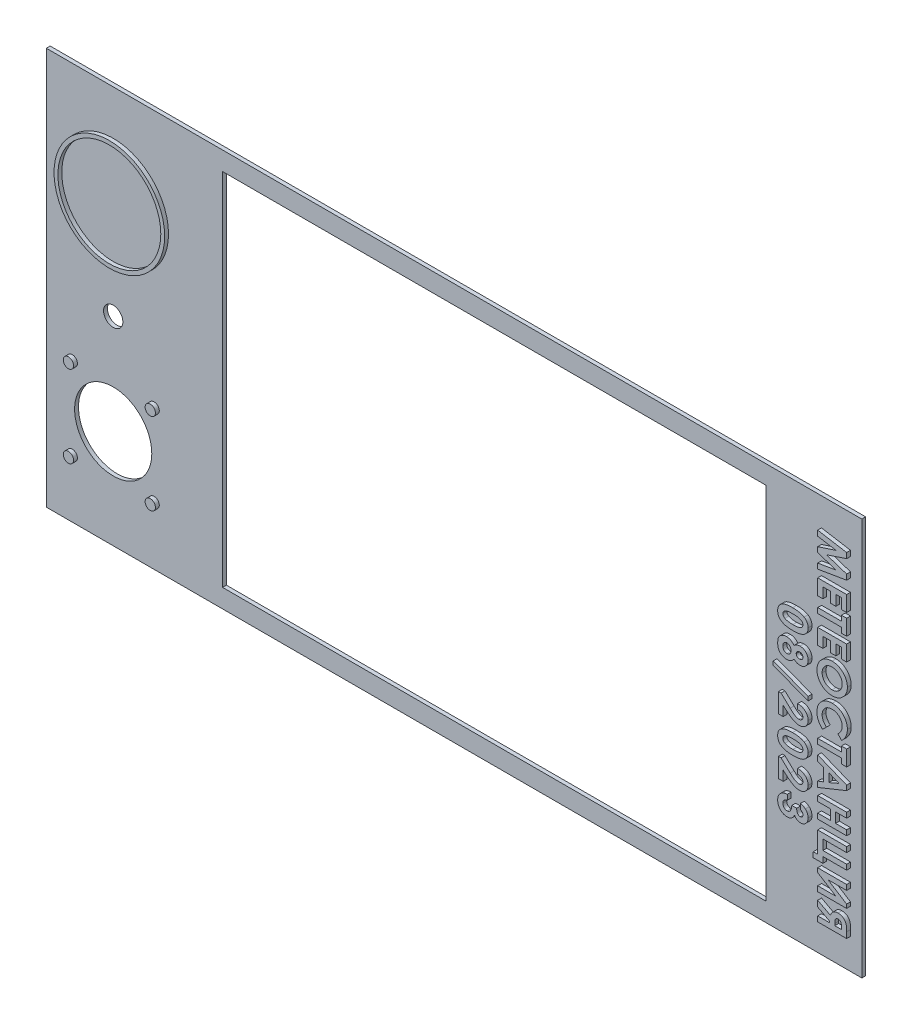
SolidWorks part; units mm, degrees
ref_plane "Спереди" through (0, 0, 0) normal (0, 0, 1) x (1, 0, 0)
ref_plane "Сверху" through (0, 0, 0) normal (0, 1, 0) x (1, 0, 0)
ref_plane "Справа" through (0, 0, 0) normal (1, 0, 0) x (0, 0, -1)
sketch "Эскиз1" plane through (0, 0, 0) normal (0, 0, 1) x (1, 0, 0)
  line L1 (-35.4452, 29.8258) -> (96.5548, 29.8258)
  line L2 (-35.4452, 29.8258) -> (-35.4452, -37.1742)
  line L3 (-35.4452, -37.1742) -> (96.5548, -37.1742)
  line L4 (96.5548, 29.8258) -> (96.5548, -37.1742)
  dimension "D1" = 67
  dimension "D2" = 132
extrude "Бобышка-Вытянуть1" add sketch "Эскиз1" against normal blind 10
shell "Оболочка1" thickness 2 removed face at (30.5548, -3.6742, -10) removed face at (30.5548, -3.6742, 0)
sketch "Эскиз3" plane through (0, 0, -10) normal (0, 0, -1) x (-1, 0, 0)
  line L1 (-96.5548, 29.8258) -> (35.4452, 29.8258)
  line L2 (-96.5548, 29.8258) -> (-96.5548, -37.1742)
  line L3 (-96.5548, -37.1742) -> (35.4452, -37.1742)
  line L4 (35.4452, 29.8258) -> (35.4452, -37.1742)
  line L5 (34.6452, -36.3742) -> (-95.7548, -36.3742)
  line L6 (34.6452, -36.3742) -> (34.6452, 29.0258)
  line L7 (34.6452, 29.0258) -> (-95.7548, 29.0258)
  line L8 (-95.7548, -36.3742) -> (-95.7548, 29.0258)
  dimension "D1" = 0.8
  dimension "D2" = 0.8
  dimension "D3" = 0.8
  dimension "D4" = 0.8
extrude "Бобышка-Вытянуть2" add sketch "Эскиз3" along normal blind 2
sketch "Эскиз4" plane through (0, 0, 0) normal (0, 0, 1) x (1, 0, 0)
  line L1 (-35.4452, 29.8258) -> (96.5548, 29.8258)
  line L2 (-35.4452, 29.8258) -> (-35.4452, -37.1742)
  line L3 (-35.4452, -37.1742) -> (96.5548, -37.1742)
  line L4 (96.5548, 29.8258) -> (96.5548, -37.1742)
extrude "Бобышка-Вытянуть3" add sketch "Эскиз4" against normal blind 2
sketch "Эскиз5" plane through (0, 0, -2) normal (0, 0, -1) x (-1, 0, 0)
  line L0 (33.4452, 27.8258) -> (-94.5548, 27.8258) construction
  line L1 (-85.5548, 24.8258) -> (-0.5548, 24.8258)
  line L2 (-85.5548, 24.8258) -> (-85.5548, -32.1742)
  line L3 (-85.5548, -32.1742) -> (-0.5548, -32.1742)
  line L4 (-0.5548, 24.8258) -> (-0.5548, -32.1742)
  line L5 (-94.5548, -35.1742) -> (33.4452, -35.1742) construction
  line L6 (-94.5548, 27.8258) -> (-94.5548, -35.1742) construction
  dimension "D1" = 3
  dimension "D2" = 3
  dimension "D3" = 9
  dimension "D4" = 85
  dimension "D5" = 57
extrude "Вырез-Вытянуть2" cut sketch "Эскиз5" against normal blind 2
sketch "Эскиз6" plane through (0, 0, -2) normal (0, 0, -1) x (-1, 0, 0)
  circle A0 centre (21.9452, -3.6742) radius 3.5
  dimension "D1" = 7
extrude "Вырез-Вытянуть3" cut sketch "Эскиз6" against normal blind 2
sketch "Эскиз7" plane through (0, 0, 0) normal (0, 0, 1) x (1, 0, 0)
  line L5 (-32.9452, 27.3258) -> (94.0548, 27.3258)
  line L6 (-32.9452, 27.3258) -> (-32.9452, -34.6742)
  line L7 (-32.9452, -34.6742) -> (94.0548, -34.6742)
  line L8 (94.0548, 27.3258) -> (94.0548, -34.6742)
extrude "Вырез-Вытянуть4" cut sketch "Эскиз7" against normal blind 0.8
sketch "Эскиз8" plane through (95.7548, 0, 0) normal (-1, 0, 0) x (0, 0, 1)
  line L1 (-11.2, 23.4258) -> (-12, 23.4258)
  line L2 (-11.2, 23.4258) -> (-11.2, 5.6258)
  line L3 (-11.2, 5.6258) -> (-12, 5.6258)
  line L4 (-12, 23.4258) -> (-12, 5.6258)
  line L5 (-11.2, -12.9742) -> (-12, -12.9742)
  line L6 (-11.2, -12.9742) -> (-11.2, -30.7742)
  line L7 (-11.2, -30.7742) -> (-12, -30.7742)
  line L8 (-12, -12.9742) -> (-12, -30.7742)
  dimension "D1" = 17.8
  dimension "D2" = 17.8
extrude "Бобышка-Вытянуть4" add sketch "Эскиз8" along normal blind 1.2
sketch "Эскиз9" plane through (0, 0, -12) normal (0, 0, -1) x (-1, 0, 0)
  line L1 (-94.5548, 27.8258) -> (33.4452, 27.8258)
  line L2 (-94.5548, 27.8258) -> (-94.5548, -35.1742)
  line L3 (-94.5548, -35.1742) -> (33.4452, -35.1742)
  line L4 (33.4452, 27.8258) -> (33.4452, -35.1742)
  line L5 (34.6452, -36.3742) -> (-95.7548, -36.3742)
  line L6 (34.6452, -36.3742) -> (34.6452, 29.0258)
  line L7 (34.6452, 29.0258) -> (-95.7548, 29.0258)
  line L8 (-95.7548, -36.3742) -> (-95.7548, 29.0258)
extrude "Бобышка-Вытянуть5" add sketch "Эскиз9" against normal blind 2
sketch "Эскиз10" plane through (0, 0, -12) normal (0, 0, -1) x (-1, 0, 0)
  line L0 (33.4452, 27.8258) -> (-94.5548, 27.8258) construction
  line L1 (-96.5548, 29.8258) -> (35.4452, 29.8258)
  line L2 (-96.5548, 29.8258) -> (-96.5548, -37.1742)
  line L3 (-96.5548, -37.1742) -> (35.4452, -37.1742)
  line L4 (35.4452, 29.8258) -> (35.4452, -37.1742)
  line L5 (34.2452, -35.9742) -> (-95.3548, -35.9742)
  line L6 (34.2452, -35.9742) -> (34.2452, 28.6258)
  line L7 (34.2452, 28.6258) -> (-95.3548, 28.6258)
  line L8 (-95.3548, -35.9742) -> (-95.3548, 28.6258)
  line L9 (-94.5548, 27.8258) -> (-94.5548, -35.1742) construction
  line L10 (-94.5548, -35.1742) -> (33.4452, -35.1742) construction
  line L11 (33.4452, -35.1742) -> (33.4452, 27.8258) construction
  dimension "D1" = 0.8
  dimension "D2" = 0.8
  dimension "D3" = 0.8
  dimension "D4" = 0.8
extrude "Вырез-Вытянуть5" cut sketch "Эскиз10" against normal blind 2
sketch "Эскиз11" plane through (0, 0, -2) normal (0, 0, -1) x (-1, 0, 0)
  line L0 (-94.5548, 27.8258) -> (-94.5548, -35.1742) construction
  line L1 (-87.0548, 27.0758) -> (7.9452, 27.0758)
  line L2 (-87.0548, 27.0758) -> (-87.0548, -34.4242)
  line L3 (-87.0548, -34.4242) -> (7.9452, -34.4242)
  line L4 (7.9452, 27.0758) -> (7.9452, -34.4242)
  line L5 (33.4452, 27.8258) -> (-94.5548, 27.8258) construction
  line L6 (-94.5548, -35.1742) -> (33.4452, -35.1742) construction
  dimension "D1" = 7.5
  dimension "D2" = 95
  dimension "D3" = 0.75
  dimension "D4" = 0.75
  dimension "D5" = 61.5
extrude "Вырез-Вытянуть6" cut sketch "Эскиз11" against normal blind 2
sketch "Эскиз12" plane through (0, 0, 0) normal (0, 0, 1) x (1, 0, 0)
  line L0 (96.5548, -37.1742) -> (96.5548, 29.8258) construction
  line L1 (-33.4452, 27.8258) -> (94.5548, 27.8258)
  line L2 (-33.4452, 27.8258) -> (-33.4452, -35.1742)
  line L3 (-33.4452, -35.1742) -> (94.5548, -35.1742)
  line L4 (94.5548, 27.8258) -> (94.5548, -35.1742)
  line L5 (-35.4452, -37.1742) -> (96.5548, -37.1742) construction
  line L6 (-35.4452, 29.8258) -> (-35.4452, -37.1742) construction
  line L7 (96.5548, 29.8258) -> (-35.4452, 29.8258) construction
  dimension "D1" = 2
  dimension "D2" = 2
  dimension "D3" = 2
  dimension "D4" = 2
extrude "Вырез-Вытянуть7" cut sketch "Эскиз12" against normal blind 0.8
sketch "Эскиз14" plane through (0, 0, -2) normal (0, 0, -1) x (-1, 0, 0)
  line L0 (33.4452, 27.8258) -> (-94.5548, 27.8258) construction
  line L1 (-94.5548, -35.1742) -> (33.4452, -35.1742) construction
  line L2 (-94.5548, -28.0242) -> (-94.5548, -35.1742)
  line L3 (-94.5548, 27.8258) -> (-94.5548, -35.1742) construction
  line L4 (7.9452, -34.4242) -> (7.9452, 27.0758) construction
  line L5 (-87.0548, 27.0758) -> (-87.0548, -34.4242) construction
  line L6 (-94.5548, -35.1742) -> (-87.5548, -35.1742)
  line L7 (-87.5548, -35.1742) -> (-87.5548, -31.5242)
  line L9 (-91.0548, -28.0242) -> (-94.5548, -28.0242)
  line L11 (-87.5548, 24.1758) -> (-87.5548, 27.8258)
  line L12 (-87.5548, 27.8258) -> (-94.5548, 27.8258)
  line L13 (-94.5548, 27.8258) -> (-94.5548, 20.6758)
  line L14 (-94.5548, 20.6758) -> (-91.0548, 20.6758)
  line L15 (7.4452, 24.1758) -> (7.4452, 27.8258)
  line L16 (7.4452, 27.8258) -> (14.4452, 27.8258)
  line L17 (33.4452, 27.8258) -> (-94.5548, 27.8258) construction
  line L18 (14.4452, 27.8258) -> (14.4452, 24.1758)
  line L19 (7.4452, -31.5242) -> (7.4452, -35.1742)
  line L20 (7.4452, -35.1742) -> (14.4452, -35.1742)
  line L21 (-94.5548, -35.1742) -> (33.4452, -35.1742) construction
  line L22 (14.4452, -35.1742) -> (14.4452, -31.5242)
  circle A0 centre (-91.0548, 24.1758) radius 1.2
  circle A1 centre (-91.0548, -31.5242) radius 1.2
  circle A2 centre (10.9452, 24.1758) radius 1.2
  circle A3 centre (10.9452, -31.5242) radius 1.2
  arc A4 (-91.0548, -28.0242) -> (-87.5548, -31.5242) centre (-91.0548, -31.5242) cw
  arc A5 (-87.5548, 24.1758) -> (-91.0548, 20.6758) centre (-91.0548, 24.1758) cw
  arc A6 (7.4452, 24.1758) -> (14.4452, 24.1758) centre (10.9452, 24.1758) ccw
  arc A7 (14.4452, -31.5242) -> (7.4452, -31.5242) centre (10.9452, -31.5242) ccw
  dimension "D1" = 3.65
  dimension "D2" = 3.65
  dimension "D5" = 3.5
  dimension "D6" = 3.5
  dimension "D7" = 102
  dimension "D8" = 102
  dimension "D9" = 55.7
  dimension "D10" = 3
  dimension "D11" = 4
extrude "Бобышка-Вытянуть6" add sketch "Эскиз14" along normal blind 1.8
sketch "Эскиз15" plane through (0, 0, -0.8) normal (0, 0, 1) x (1, 0, 0)
  line L1 (-7.9452, 27.0758) -> (-7.4452, 27.0758)
  line L2 (-7.9452, 27.0758) -> (-7.9452, -34.4242)
  line L3 (-7.9452, -34.4242) -> (-7.4452, -34.4242)
  line L4 (-7.4452, 27.0758) -> (-7.4452, -34.4242)
extrude "Бобышка-Вытянуть7" add sketch "Эскиз15" against normal up to surface (1.2 mm away) up to face at (-7.6645, -32.515, -2)
sketch "Эскиз16" plane through (0, 0, -2) normal (0, 0, -1) x (-1, 0, 0)
  line L0 (-87.5548, -35.1742) -> (-87.5548, -31.5242) construction
  line L1 (-87.0548, 27.0758) -> (-87.5548, 27.0758)
  line L2 (-87.0548, 27.0758) -> (-87.0548, -34.4242)
  line L3 (-87.0548, -34.4242) -> (-87.5548, -34.4242)
  line L4 (-87.5548, 27.0758) -> (-87.5548, -34.4242)
extrude "Вырез-Вытянуть8" cut sketch "Эскиз16" against normal blind 1.8
sketch "Эскиз17" plane through (0, 0, -2) normal (0, 0, -1) x (-1, 0, 0)
  circle A0 centre (-91.0548, 24.1758) radius 1.2
  circle A1 centre (-91.0548, -31.5242) radius 1.2
  circle A2 centre (10.9452, -31.5242) radius 1.2
  circle A5 centre (10.9452, 24.1758) radius 1.2
extrude "Вырез-Вытянуть9" cut sketch "Эскиз17" against normal blind 1.8
sketch "Эскиз19" plane through (0, 0, -2) normal (0, 0, -1) x (-1, 0, 0)
  line L0 (33.4452, -35.1742) -> (33.4452, 27.8258) construction
  line L1 (14.4452, -35.1742) -> (33.4452, -35.1742) construction
  line L2 (14.4452, -35.1742) -> (14.4452, -31.5242) construction
  circle A0 centre (22.4452, -19.1742) radius 3.5
  point P8 (14.4452, -33.3492)
  dimension "D1" = 11
  dimension "D2" = 16
  dimension "D3" = 8
extrude "Вырез-Вытянуть11" cut sketch "Эскиз19" against normal blind 1.8
sketch "Эскиз22" plane through (0, 0, -2) normal (0, 0, -1) x (-1, 0, 0)
  circle A0 centre (21.9452, -3.6742) radius 3.5
extrude "Бобышка-Вытянуть9" add sketch "Эскиз22" against normal up to surface (1.2 mm away) up to face at (-18.9452, -19.1742, -0.8)
sketch "Эскиз23" plane through (0, 0, -2) normal (0, 0, -1) x (-1, 0, 0)
  line L2 (16.6952, 2.5758) -> (28.1952, 2.5758)
  line L3 (16.6952, 2.5758) -> (16.6952, 17.5758)
  line L4 (16.6952, 17.5758) -> (28.1952, 17.5758)
  line L5 (28.1952, 2.5758) -> (28.1952, 17.5758)
  circle A2 centre (22.4452, -3.6742) radius 1.5
  dimension "D5" = 11.5
  dimension "D7" = 15
extrude "Вырез-Вытянуть13" cut sketch "Эскиз23" against normal blind 1.8
sketch "Эскиз24" plane through (0, 0, -2) normal (0, 0, -1) x (-1, 0, 0)
  circle A0 centre (22.4452, -3.6742) radius 1.5
  circle A1 centre (22.4452, -3.6742) radius 2.5
extrude "Бобышка-Вытянуть10" add sketch "Эскиз24" along normal blind 1
chamfer "Фаска1" distance 2 angle 35 4 edges at (92.2548, -31.5242, -0.8) (92.2548, 24.1758, -0.8) (-9.7452, -31.5242, -0.8) (-9.7452, 24.1758, -0.8) first distance on face at (-22.4452, 10.0758, -0.8)
sketch "Эскиз25" plane through (0, 0, -2) normal (0, 0, -1) x (-1, 0, 0)
  line L0 (33.4452, -35.1742) -> (33.4452, 27.8258) construction
  line L1 (29.9452, -0.1742) -> (33.4452, -0.1742)
  line L2 (33.4452, -35.1742) -> (33.4452, 27.8258) construction
  line L3 (33.4452, -0.1742) -> (33.4452, -7.1742)
  line L4 (33.4452, -7.1742) -> (29.9452, -7.1742)
  arc A0 (29.9452, -0.1742) -> (29.9452, -7.1742) centre (29.9452, -3.6742) ccw
  circle A1 centre (29.9452, -3.6742) radius 1.2
  dimension "D1" = 3.5
extrude "Бобышка-Вытянуть11" add sketch "Эскиз25" along normal up to surface (10 mm away) up to face at (30.5548, -3.6742, -12)
sketch "Эскиз26" plane through (95.3548, 0, 0) normal (1, 0, 0) x (0, 0, -1)
  line L0 (10, 28.6258) -> (10, -35.9742) construction
  line L1 (10, 18.8258) -> (11.2, 18.8258)
  line L2 (10, 18.8258) -> (10, 3.2258)
  line L3 (10, 3.2258) -> (11.2, 3.2258)
  line L4 (11.2, 18.8258) -> (11.2, 3.2258)
  line L5 (10, 28.6258) -> (12, 28.6258) construction
  line L6 (10, -35.9742) -> (12, -35.9742) construction
  line L7 (10, -26.1742) -> (11.2, -26.1742)
  line L8 (10, -26.1742) -> (10, -10.5742)
  line L9 (10, -10.5742) -> (11.2, -10.5742)
  line L10 (11.2, -26.1742) -> (11.2, -10.5742)
  dimension "D1" = 9.8
  dimension "D2" = 15.6
  dimension "D3" = 1.2
  dimension "D4" = 9.8
  dimension "D5" = 15.6
  dimension "D6" = 1.2
  dimension "D7" = 13.8
extrude "Вырез-Вытянуть14" cut sketch "Эскиз26" against normal blind 10
sketch "Эскиз28" plane through (0, 0, 0) normal (0, 0, 1) x (1, 0, 0)
  line L1 (-33.4452, 27.8258) -> (94.5548, 27.8258)
  line L2 (-33.4452, 27.8258) -> (-33.4452, -35.1742)
  line L3 (-33.4452, -35.1742) -> (94.5548, -35.1742)
  line L4 (94.5548, 27.8258) -> (94.5548, -35.1742)
  line L5 (-7.4452, 27.0758) -> (87.5548, 27.0758)
  line L6 (-7.4452, 27.0758) -> (-7.4452, -34.4242)
  line L7 (-7.4452, -34.4242) -> (87.5548, -34.4242)
  line L8 (87.5548, 27.0758) -> (87.5548, -34.4242)
  circle A0 centre (-22.4452, -19.1742) radius 3.5
  circle A1 centre (-22.4452, -3.6742) radius 1.5
  circle A2 centre (-22.4452, 11.7012) radius 5.8746
extrude "Бобышка-Вытянуть12" add sketch "Эскиз28" along normal blind 0.6 from offset 10 separate body
sketch "Эскиз29" plane through (0, 0, 0) normal (0, 0, 1) x (1, 0, 0)
  line L1 (-37.4213, 32.2377) -> (98.9585, 32.2377)
  line L2 (-37.4213, 32.2377) -> (-37.4213, -38.7311)
  line L3 (-37.4213, -38.7311) -> (98.9585, -38.7311)
  line L4 (98.9585, 32.2377) -> (98.9585, -38.7311)
extrude "Вырез-Вытянуть15" cut sketch "Эскиз29" against normal through all
sketch "Эскиз30" plane through (0, 0, 10.6) normal (0, 0, 1) x (1, 0, 0)
  line L0 (94.5548, -35.1742) -> (94.5548, 27.8258) construction
  line L1 (0.5548, 24.3258) -> (85.5548, 24.3258)
  line L2 (0.5548, 24.3258) -> (0.5548, -31.6742)
  line L3 (0.5548, -31.6742) -> (85.5548, -31.6742)
  line L4 (85.5548, 24.3258) -> (85.5548, -31.6742)
  line L5 (94.5548, 27.8258) -> (-33.4452, 27.8258) construction
  line L7 (-33.4452, -35.1742) -> (94.5548, -35.1742) construction
  line L9 (-7.4452, 27.0758) -> (87.5548, 27.0758)
  line L10 (-7.4452, 27.0758) -> (-7.4452, -34.4242)
  line L11 (-7.4452, -34.4242) -> (87.5548, -34.4242)
  line L12 (87.5548, 27.0758) -> (87.5548, -34.4242)
  dimension "D1" = 9
  dimension "D2" = 56
  dimension "D3" = 85
  dimension "D4" = 3.5
  dimension "D5" = 3.5
extrude "Бобышка-Вытянуть13" add sketch "Эскиз30" against normal up to surface (0.6 mm away) up to face at (-16.5705, 11.7012, 10)
sketch "Эскиз31" plane through (0, 0, 10.6) normal (0, 0, 1) x (1, 0, 0)
  line L0 (94.5548, -35.1742) -> (94.5548, 27.8258) construction
  line L1 (-33.2452, 27.6258) -> (94.3548, 27.6258)
  line L2 (-33.2452, 27.6258) -> (-33.2452, -34.9742)
  line L3 (-33.2452, -34.9742) -> (94.3548, -34.9742)
  line L4 (94.3548, 27.6258) -> (94.3548, -34.9742)
  line L5 (-33.4452, -35.1742) -> (94.5548, -35.1742) construction
  line L6 (94.5548, 27.8258) -> (-33.4452, 27.8258) construction
  line L7 (-33.4452, 27.8258) -> (-33.4452, -35.1742) construction
  line L9 (-35.9833, 28.6621) -> (96.2638, 28.6621)
  line L10 (-35.9833, 28.6621) -> (-35.9833, -36.0106)
  line L11 (-35.9833, -36.0106) -> (96.2638, -36.0106)
  line L12 (96.2638, 28.6621) -> (96.2638, -36.0106)
  dimension "D1" = 0.2
  dimension "D2" = 0.2
  dimension "D3" = 0.2
  dimension "D4" = 0.2
extrude "Вырез-Вытянуть16" cut sketch "Эскиз31" against normal blind 0.6
sketch "Эскиз32" plane through (0, 0, 10.6) normal (0, 0, 1) x (1, 0, 0)
  circle A0 centre (-22.4452, 11.7012) radius 8
  circle A1 centre (-22.4452, 11.7012) radius 9
extrude "Бобышка-Вытянуть14" add sketch "Эскиз32" along normal blind 0.6
sketch "Эскиз33" plane through (0, 0, 10.6) normal (0, 0, 1) x (1, 0, 0)
  circle A0 centre (-22.4452, 11.7012) radius 5.8746
extrude "Бобышка-Вытянуть15" add sketch "Эскиз33" against normal up to surface (0.6 mm away) up to face at (43.0548, -3.6742, 10)
sketch "Эскиз34" plane through (0, 0, 10.6) normal (0, 0, 1) x (1, 0, 0)
  circle A1 centre (-28.4556, -13.1638) radius 0.6
  circle A2 centre (-16.4348, -13.1638) radius 0.6
  circle A3 centre (-16.4348, -25.1846) radius 0.6
  circle A4 centre (-28.4556, -25.1846) radius 0.6
extrude "Бобышка-Вытянуть16" add sketch "Эскиз34" along normal blind 0.6
sketch "Эскиз35" plane through (0, 0, 10.6) normal (0, 0, 1) x (1, 0, 0)
  text T0 "МЕТЕОСТАНЦИЯ" font "Century Gothic" height 4.5
  text T1 "02/0/.23" font "Century Gothic" height 4.5
extrude "Бобышка-Вытянуть17" add sketch "Эскиз35" along normal blind 0.6
sketch "Эскиз37" plane through (0, 0, 11.2) normal (0, 0, 1) x (1, 0, 0)
  line L1 (-8.344, 12.2833) -> (0, 12.2833)
  line L2 (-8.344, 12.2833) -> (-8.344, -20.1798)
  line L3 (-8.344, -20.1798) -> (0, -20.1798)
  line L4 (0, 12.2833) -> (0, -20.1798)
extrude "Вырез-Вытянуть18" cut sketch "Эскиз37" against normal up to surface (0.6 mm away) up to face at (89.6987, 4.247, 10.6)
sketch "Эскиз38" plane through (0, 0, 10.6) normal (0, 0, 1) x (1, 0, 0)
  text T0 "02/09/2023" font "Century Gothic" height 4.5
extrude "Бобышка-Вытянуть18" add sketch "Эскиз38" along normal blind 0.6
sketch "Эскиз39" plane through (0, 0, 10.6) normal (0, 0, 1) x (1, 0, 0)
  circle A0 centre (-22.4452, -19.1742) radius 6
extrude "Вырез-Вытянуть19" cut sketch "Эскиз39" against normal blind 0.6
sketch "Эскиз40" plane through (0, 0, 11.2) normal (0, 0, 1) x (1, 0, 0)
  line L1 (-7.7859, 14.083) -> (-0.9762, 14.083)
  line L2 (-7.7859, 14.083) -> (-7.7859, -20.6099)
  line L3 (-7.7859, -20.6099) -> (-0.9762, -20.6099)
  line L4 (-0.9762, 14.083) -> (-0.9762, -20.6099)
extrude "Вырез-Вытянуть20" cut sketch "Эскиз40" against normal up to surface (0.6 mm away) up to face at (89.6987, 4.247, 10.6)
sketch "Эскиз41" plane through (0, 0, 10.6) normal (0, 0, 1) x (1, 0, 0)
  text T0 "08/2023" font "Century Gothic" height 5
extrude "Бобышка-Вытянуть19" add sketch "Эскиз41" along normal blind 0.6
sketch "Эскиз42" plane through (0, 0, 10.6) normal (0, 0, 1) x (1, 0, 0)
  line L2 (0.5548, -31.6742) -> (85.5548, -31.6742) construction
  line L3 (-5.4452, 24.3258) -> (79.0548, 24.3258)
  line L4 (-5.4452, 24.3258) -> (-5.4452, -31.6742)
  line L5 (-5.4452, -31.6742) -> (79.0548, -31.6742)
  line L6 (79.0548, 24.3258) -> (79.0548, -31.6742)
  line L7 (-33.2452, 27.6258) -> (-33.2452, -34.9742) construction
  line L8 (94.3548, -34.9742) -> (94.3548, 27.6258) construction
  dimension "D1" = 27.8
  dimension "D2" = 15.3
  dimension "D3" = 84.5
extrude "Вырез-Вытянуть23" cut sketch "Эскиз42" against normal blind 10
sketch "Эскиз45" plane through (0, 0, 10.6) normal (0, 0, 1) x (1, 0, 0)
  line L0 (-5.4452, -31.6742) -> (85.5548, -31.6742) construction
  line L1 (85.5548, 24.3258) -> (79.0548, 24.3258)
  line L2 (85.5548, 24.3258) -> (85.5548, -31.6742)
  line L3 (85.5548, -31.6742) -> (79.0548, -31.6742)
  line L4 (79.0548, 24.3258) -> (79.0548, -31.6742)
  line L6 (-5.4452, -19.7496) -> (-5.4452, -31.6742) construction
  dimension "D1" = 84.5
extrude "Бобышка-Вытянуть20" add sketch "Эскиз45" against normal up to surface (0.6 mm away) up to face at (-16.4452, -19.1742, 10)
sketch "Эскиз46" plane through (0, 0, 11.2) normal (0, 0, 1) x (1, 0, 0)
  line L1 (-9.3758, 13.3336) -> (-1.1731, 13.3336)
  line L2 (-9.3758, 13.3336) -> (-9.3758, -22.5398)
  line L3 (-9.3758, -22.5398) -> (-1.1731, -22.5398)
  line L4 (-1.1731, 13.3336) -> (-1.1731, -22.5398)
extrude "Вырез-Вытянуть24" cut sketch "Эскиз46" against normal up to surface (0.6 mm away) up to face at (89.6987, 4.247, 10.6)
sketch "Эскиз47" plane through (0, 0, 10.6) normal (0, 0, 1) x (1, 0, 0)
  line L1 (-32.8452, 27.2258) -> (93.9548, 27.2258)
  line L2 (-32.8452, 27.2258) -> (-32.8452, -34.5742)
  line L3 (-32.8452, -34.5742) -> (93.9548, -34.5742)
  line L4 (93.9548, 27.2258) -> (93.9548, -34.5742)
  line L5 (94.3548, -34.9742) -> (-33.2452, -34.9742)
  line L6 (94.3548, -34.9742) -> (94.3548, 27.6258)
  line L7 (94.3548, 27.6258) -> (-33.2452, 27.6258)
  line L8 (-33.2452, -34.9742) -> (-33.2452, 27.6258)
  dimension "D1" = 0.4
  dimension "D2" = 0.4
  dimension "D3" = 0.4
  dimension "D4" = 0.4
extrude "Вырез-Вытянуть25" cut sketch "Эскиз47" against normal blind 10
sketch "Эскиз48" plane through (0, 0, 10.6) normal (0, 0, 1) x (1, 0, 0)
  text T0 "08/2023" font "Century Gothic" height 4.5
extrude "Бобышка-Вытянуть22" add sketch "Эскиз48" along normal blind 0.6
sketch "Эскиз49" plane through (0, 0, 11.2) normal (0, 0, 1) x (1, 0, 0)
  line L3 (-29.3769, -12.2043) -> (-15.4744, -12.2043)
  line L4 (-29.3769, -12.2043) -> (-29.3769, -26.1068)
  line L5 (-29.3769, -26.1068) -> (-15.4744, -26.1068)
  line L6 (-15.4744, -12.2043) -> (-15.4744, -26.1068)
extrude "Вырез-Вытянуть26" cut sketch "Эскиз49" against normal up to surface (0.6 mm away) up to face at (84.0896, -16.4976, 10.6)
sketch "Эскиз50" plane through (0, 0, 10.6) normal (0, 0, 1) x (1, 0, 0)
  circle A1 centre (-16.0812, -12.8102) radius 0.8
  circle A2 centre (-28.8091, -12.8102) radius 0.8
  circle A3 centre (-28.8091, -25.5382) radius 0.8
  circle A4 centre (-16.0812, -25.5382) radius 0.8
extrude "Бобышка-Вытянуть23" add sketch "Эскиз50" along normal blind 0.6
sketch "Эскиз51" plane through (0, 0, 11.2) normal (0, 0, 1) x (1, 0, 0)
  circle A1 centre (-22.4452, 11.7012) radius 8.6
  circle A2 centre (-22.4452, 11.7012) radius 9.4248
extrude "Вырез-Вытянуть27" cut sketch "Эскиз51" against normal up to surface (0.6 mm away) up to face at (-15.2812, -25.5382, 10.6)
